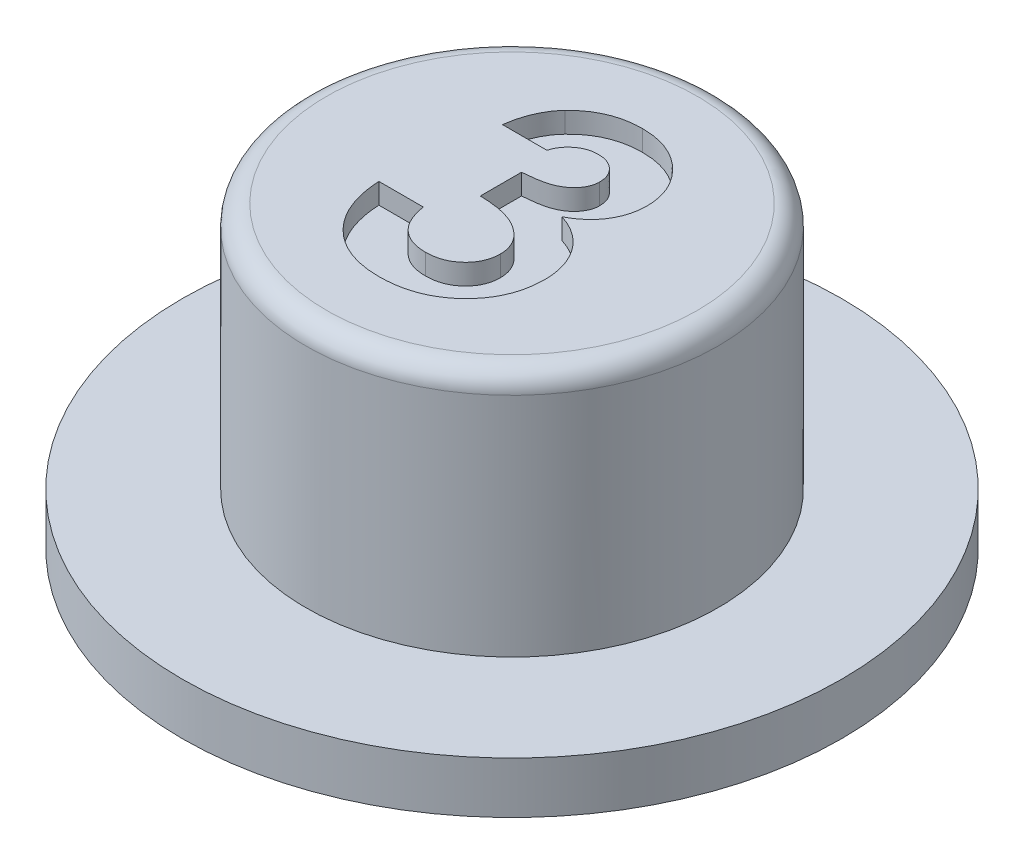
SolidWorks part; units mm, degrees
ref_plane "Front Plane" through (0, 0, 0) normal (0, 0, 1) x (1, 0, 0)
ref_plane "Top Plane" through (0, 0, 0) normal (0, 1, 0) x (1, 0, 0)
ref_plane "Right Plane" through (0, 0, 0) normal (1, 0, 0) x (0, 0, -1)
sketch "Sketch1" plane through (0, 0, 0) normal (0, 0, 1) x (1, 0, 0)
  line L1 (0, 7.25) -> (5, 7.25)
  line L2 (5, 7.25) -> (5, 1.25)
  line L3 (5, 1.25) -> (8, 1.25)
  line L4 (8, 1.25) -> (8, 0)
  line L6 (0, 7.25) -> (0, 6.9292) construction
  line L7 (0, 7.25) -> (0, 0)
  line L10 (0, 0) -> (8, 0)
  dimension "D1" = 5
  dimension "D2" = 3
  dimension "D3" = 6
  dimension "D4" = 1.25
revolve "Revolve1" add sketch "Sketch1" angle 360 about L6
sketch "Sketch2" plane through (0, 0, 0) normal (0, -1, 0) x (1, 0, 0)
  line L1 (-1.75, -1.25) -> (1.75, -1.25)
  line L2 (-1.75, -1.25) -> (-1.75, 1.25)
  line L3 (-1.75, 1.25) -> (1.75, 1.25)
  line L4 (1.75, -1.25) -> (1.75, 1.25)
  line L5 (-1.75, -1.25) -> (1.75, 1.25) construction
  line L6 (-1.75, 1.25) -> (1.75, -1.25) construction
  point P0 (0, 0)
  dimension "D1" = 3.5
  dimension "D2" = 2.5
extrude "Cut-Extrude1" cut sketch "Sketch2" against normal blind 3.5 contours L3 L4 L1 L2
fillet "Fillet1" radius 0.5 1 edges at (-5, 7.25, 0)
sketch "Sketch3" plane through (0, 7.25, 0) normal (0, 1, 0) x (1, 0, 0)
  line L0 (-3.3541, -3) -> (3.3541, -3) construction
  line L1 (0, 0) -> (0, -3) construction
  circle A0 centre (0, 0) radius 4.5 construction
  text T0 "3" font "Century Gothic" height 6
  dimension "D1" = 3
extrude "Cut-Extrude2" cut sketch "Sketch3" against normal blind 0.5
